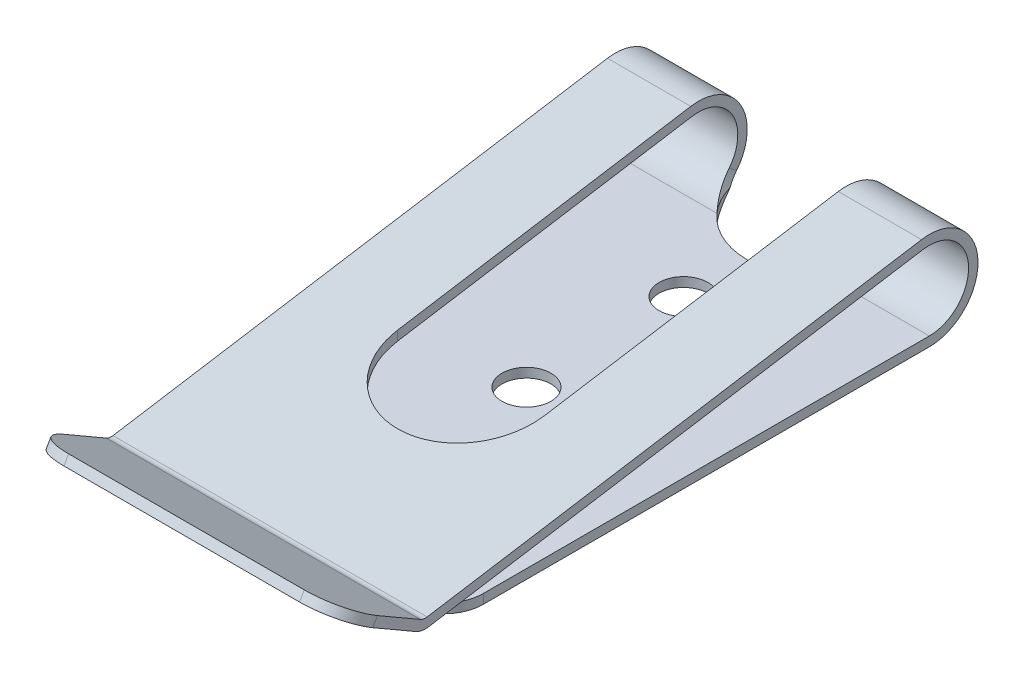
SolidWorks part; units mm, degrees
ref_plane "Front Plane" through (0, 0, 0) normal (0, 0, 1) x (1, 0, 0)
ref_plane "Top Plane" through (0, 0, 0) normal (0, 1, 0) x (1, 0, 0)
ref_plane "Right Plane" through (0, 0, 0) normal (1, 0, 0) x (0, 0, -1)
sketch "Sketch3" plane through (0, 0, 0) normal (1, 0, 0) x (0, 0, -1)
  line L1 (9.271, 0.7587) -> (-29.972, 0.7587)
  line L2 (13.208, 3.9337) -> (13.208, 15.2816) construction
  line L3 (-38.1, 5.0767) -> (-31.8837, 1.4878)
  line L4 (-32.2647, 0.8278) -> (-38.481, 4.4168)
  line L51 (8.6456, 7.8207) -> (-31.3398, 1.3876)
  line L63 (-29.972, -0.0033) -> (9.271, -0.0033)
  line L65 (8.7667, 7.0684) -> (-31.2188, 0.6353)
  line L91 (-29.972, -0.0033) -> (-29.972, 0.7587)
  line L134 (-38.481, 4.4168) -> (-38.1, 5.0767)
  line L136 (0, -0.0033) -> (0, 6.4298) construction
  line L137 (-12.7, -0.0033) -> (-12.7, 4.3865) construction
  arc A0 (9.271, 0.7587) -> (8.7667, 7.0684) centre (9.271, 3.9337) ccw
  arc A1 (8.6456, 7.8207) -> (9.271, -0.0033) centre (9.271, 3.9337) cw
  arc A2 (-32.2647, 0.8278) -> (-31.2188, 0.6353) centre (-31.471, 2.2027) ccw
  arc A3 (-31.8837, 1.4878) -> (-31.3398, 1.3876) centre (-31.471, 2.2027) ccw
  point P0 (-31.2188, 1.3876)
  point P3 (-27.2161, 0.7587)
  point P6 (-33.3235, 5.0767)
  point P7 (-26.6855, 1.7522)
  point P8 (-27.6237, 1.7468)
  point P9 (-30.4608, 3.3799)
  point P10 (-28.2609, 1.1487)
  point P11 (-28.3173, 2.019)
  point P12 (0, 0)
  point P15 (-27.6946, 1.671)
  point P16 (-16.1213, 2.1088)
  point P17 (-14.7822, 2.3105)
  point P18 (-5.9832, 3.9337)
  point P19 (0, 0)
  point P20 (-32.1417, 1.6803)
  point P21 (0, 0)
  point P22 (11.4479, 6.1168)
  point P23 (0, 0)
  point P26 (10.0755, 7.0317)
  point P27 (10.067, 7.2773)
  dimension "D5" = 1.5875
  dimension "D1" = 13.208
  dimension "D6" = 7.874
  dimension "D7" = 51.689
  dimension "D2" = 12.7
  dimension "D3" = 17.272
  dimension "D4" = 0.762
  dimension "D8" = 5.08
  dimension "D9" = 30
  dimension "D10" = 0.0762
extrude "Boss-Extrude1" add sketch "Sketch3" along normal mid plane 25.4
sketch "Sketch4" plane through (0, 0, 0) normal (0, 1, 0) x (1, 0, 0)
  line L0 (12.7, 13.208) -> (-12.7, 13.208) construction
  line L1 (12.7, 8.6456) -> (12.7, -31.3398) construction
  circle A0 centre (0, 13.208) radius 5.9614
  circle A1 centre (0, 2.0955) radius 1.9761
  circle A2 centre (0, -10.6045) radius 1.9761
  point P4 (5.9614, 13.208)
  dimension "D2" = 12.7
  dimension "D4" = 3.9522
  dimension "D1" = 6.7386
  dimension "D3" = 11.1125
extrude "Cut-Extrude1" cut sketch "Sketch4" against normal through all both and the other way through all
sketch "Sketch5" plane through (0, 0.7587, 0) normal (0, 1, 0) x (1, 0, 0)
  line L0 (-5.9614, 13.208) -> (-5.9614, -15.0571)
  line L1 (5.9614, -15.0571) -> (5.9614, 13.208)
  line L2 (-5.9614, 13.208) -> (5.9614, 13.208)
  arc A0 (5.9614, -15.0571) -> (-5.9614, -15.0571) centre (0, -15.0571) cw
  point P3 (0, -21.0185)
  point P4 (0, 0)
  point P5 (0, 0)
  point P7 (6.5554, 23.8311)
  point P9 (8.2627, 23.8311)
  point P10 (5.9614, 13.208)
  point P17 (0, 0)
  point P18 (0, 0)
  point P20 (5.9614, 23.8311)
  point P21 (-2.2252, -17.8986)
  point P23 (0, 0)
  point P24 (0, -17.2105)
  point P26 (0, 0)
  dimension "D1" = 10.414
extrude "Cut-Extrude2" cut sketch "Sketch5" along normal through all
fillet "Fillet1" radius 3.175 4 edges at (12.7, 4.7468, 38.2905) (-12.7, 4.7468, 38.2905) (-12.7, 0.3777, 29.972) (12.7, 0.3777, 29.972)
fillet "Fillet2" radius 2.54 2 edges at (5.9614, 0.7587, -10.435) (-5.9614, 0.7587, -10.435)
equation "\"thk\"= 0.03"
